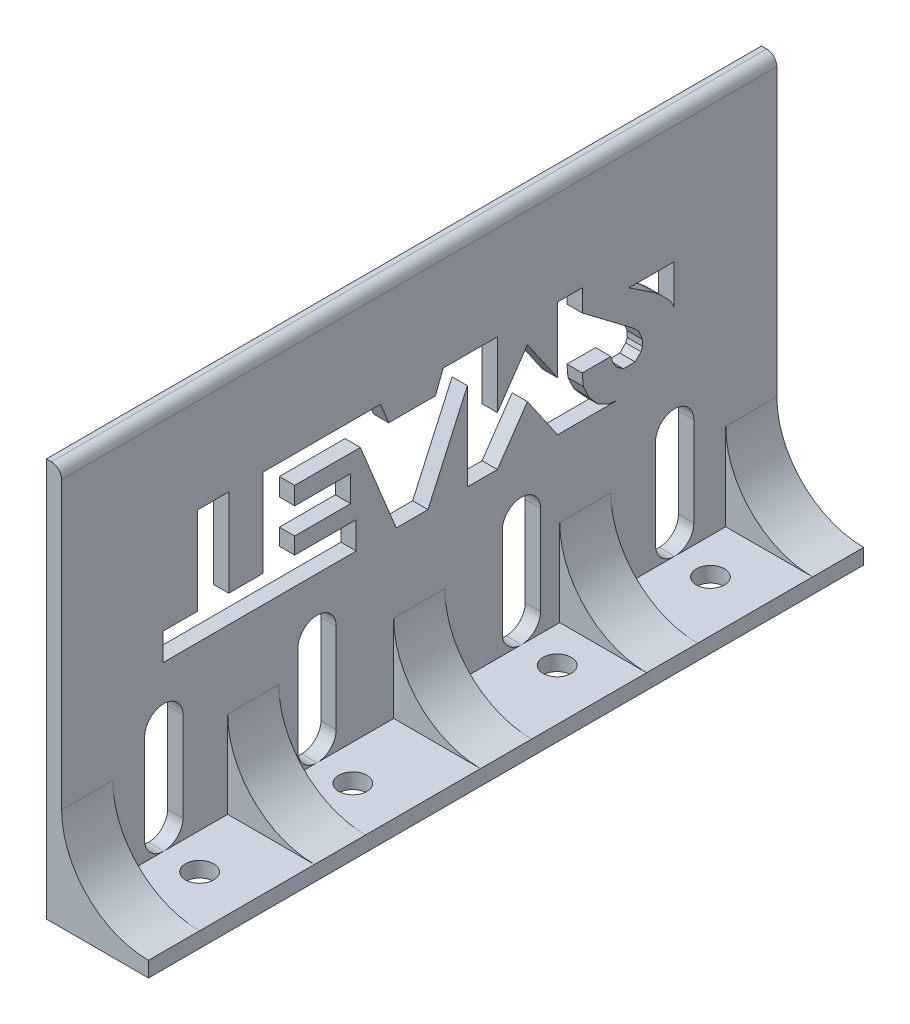
SolidWorks part; units mm, degrees
ref_plane "Front Plane" through (0, 0, 0) normal (0, 0, 1) x (1, 0, 0)
ref_plane "Top Plane" through (0, 0, 0) normal (0, 1, 0) x (1, 0, 0)
ref_plane "Right Plane" through (0, 0, 0) normal (1, 0, 0) x (0, 0, -1)
sketch "Sketch1" plane through (0, 0, 0) normal (0, 1, 0) x (1, 0, 0)
  line L1 (0, 140) -> (20, 140)
  line L2 (0, 140) -> (0, 0)
  line L3 (0, 0) -> (20, 0)
  line L4 (20, 140) -> (20, 0)
  dimension "D1" = 140
  dimension "D2" = 20
extrude "Boss-Extrude1" add sketch "Sketch1" along normal blind 3
sketch "Sketch2" plane through (0, 3, 0) normal (0, 1, 0) x (1, 0, 0)
  line L0 (0, 0) -> (20, 0) construction
  line L1 (0, 140) -> (3, 140)
  line L2 (0, 140) -> (0, 0)
  line L3 (0, 0) -> (3, 0)
  line L4 (3, 140) -> (3, 0)
  dimension "D1" = 3
extrude "Boss-Extrude2" add sketch "Sketch2" along normal blind 75
sketch "Sketch4" plane through (0, 0, 0) normal (0, -1, 0) x (1, 0, 0)
  line L0 (10, -120) -> (10, -20) construction
  line L1 (0, 0) -> (20, 0) construction
  line L2 (0, -140) -> (0, 0) construction
  circle A0 centre (10, -20) radius 2.75
  circle A2 centre (10, -50) radius 2.75
  circle A3 centre (10, -120) radius 2.75
  circle A4 centre (10, -90) radius 2.75
  point P6 (10, -70)
  point P11 (10, 0)
  point P12 (0, 0)
  point P15 (0, -70)
  dimension "D1" = 30
  dimension "D4" = 5.5
  dimension "D2" = 30
  dimension "D3" = 100
extrude "Cut-Extrude1" cut sketch "Sketch4" against normal blind 10
sketch "Sketch11" plane through (0, 0, 0) normal (-1, 0, 0) x (0, 0, 1)
  line L0 (-82.1667, -2) -> (-330.8333, -2) construction
  line L1 (-19.8745, 35.0495) -> (-57.6685, 35.0495)
  line L2 (-57.6685, 35.0495) -> (-57.6685, 40.3757)
  line L3 (-57.6685, 40.3757) -> (-45.6207, 40.3757)
  line L4 (-45.6207, 40.3757) -> (-45.6207, 43.6286)
  line L5 (-45.6207, 43.6286) -> (-56.568, 43.6286)
  line L6 (-56.568, 43.6286) -> (-56.568, 48.7277)
  line L7 (-56.568, 48.7277) -> (-45.6207, 48.7277)
  line L8 (-45.6207, 48.7277) -> (-45.6207, 52.2076)
  line L9 (-45.6207, 52.2076) -> (-58.4743, 52.2076)
  line L10 (-58.4743, 52.2076) -> (-65.496, 35.0495)
  line L11 (-65.496, 35.0495) -> (-71.704, 35.0495)
  line L12 (-71.704, 35.0495) -> (-79.4314, 52.2076)
  line L13 (-79.4314, 52.2076) -> (-79.4314, 35.0495)
  line L14 (-91.18, 43.6286) -> (-97.089, 35.0495)
  line L15 (-97.089, 35.0495) -> (-108.6328, 35.0495)
  line L18 (-112.0774, 45.5887) -> (-101.912, 53.28)
  line L19 (-101.912, 53.28) -> (-101.912, 57.5529)
  line L20 (-101.912, 57.5529) -> (-97.089, 57.5529)
  line L21 (-97.089, 57.5529) -> (-97.089, 44.7009)
  line L22 (-97.089, 44.7009) -> (-91.18, 53.28)
  line L23 (-91.18, 53.28) -> (-85.2893, 44.7009)
  line L24 (-85.2893, 44.7009) -> (-85.2893, 57.5529)
  line L25 (-62.4205, 57.5529) -> (-39.4375, 57.5529)
  line L26 (-39.4375, 57.5529) -> (-39.4375, 40.3757)
  line L27 (-39.4375, 40.3757) -> (-32.7115, 40.3757)
  line L28 (-32.7115, 40.3757) -> (-32.7115, 57.5529)
  line L29 (-32.7115, 57.5529) -> (-26.5718, 57.5529)
  line L30 (-26.5718, 57.5529) -> (-26.5718, 40.3757)
  line L31 (-26.5718, 40.3757) -> (-19.8745, 40.3757)
  line L32 (-19.8745, 40.3757) -> (-19.8745, 35.0495)
  line L33 (-119.871, 52.9786) -> (-111.0302, 52.9786)
  line L34 (-111.0302, 52.9786) -> (-115.1097, 50.2969)
  line L38 (-115.1097, 50.2969) -> (-115.8723, 49.7955)
  line L39 (-115.8723, 49.7955) -> (-117.2013, 48.7277)
  line L40 (-117.2013, 48.7277) -> (-119.0543, 46.8318)
  line L41 (-119.0543, 46.8318) -> (-119.5813, 46.0265)
  line L42 (-119.5813, 46.0265) -> (-119.871, 45.2733)
  line L44 (-119.871, 45.2733) -> (-119.871, 52.9786)
  line L45 (-85.2893, 57.5529) -> (-74.692, 57.5529)
  line L46 (-73.1717, 53.6017) -> (-74.692, 57.5529)
  line L47 (-64.0278, 53.6017) -> (-62.4205, 57.5529)
  line L48 (-64.0278, 53.6017) -> (-73.1717, 53.6017)
  line L52 (-91.18, 43.6286) -> (-85.2893, 35.0495)
  line L53 (-85.2893, 35.0495) -> (-79.4314, 35.0495)
  line L54 (-107.5115, 43.1186) -> (-101.912, 43.1186)
  line L55 (-101.912, 43.1186) -> (-102.1172, 40.7245)
  line L56 (-102.1172, 40.7245) -> (-103.2623, 38.2856)
  line L57 (-103.2623, 38.2856) -> (-104.8918, 36.4052)
  line L59 (-104.8918, 36.4052) -> (-106.9644, 35.3102)
  line L60 (-106.9644, 35.3102) -> (-108.6328, 35.0495)
  line L61 (-112.0774, 45.5887) -> (-112.9652, 44.7009)
  line L62 (-112.9652, 44.7009) -> (-113.708, 42.875)
  line L63 (-113.708, 42.875) -> (-113.708, 41.7402)
  line L64 (-113.708, 41.7402) -> (-113.4126, 40.9724)
  line L65 (-113.4126, 40.9724) -> (-112.2556, 39.8155)
  line L66 (-112.2556, 39.8155) -> (-109.9566, 39.8155)
  line L67 (-109.9566, 39.8155) -> (-108.6328, 40.7245)
  line L68 (-108.6328, 40.7245) -> (-108.0141, 41.6227)
  line L69 (-108.0141, 41.6227) -> (-107.5115, 43.1186)
extrude "Cut-Extrude5" cut sketch "Sketch11" against normal blind 10
sketch "Sketch13" plane through (3, 0, 0) normal (1, 0, 0) x (0, 0, -1)
  line L0 (0, 3) -> (140, 3) construction
  line L1 (22.75, 3) -> (17.25, 3) construction
  line L2 (122.75, 3) -> (117.25, 3) construction
  line L3 (92.75, 3) -> (87.25, 3) construction
  line L4 (52.75, 3) -> (47.25, 3) construction
  line L6 (16.25, 3) -> (23.75, 3)
  line L7 (16.25, 3) -> (16.25, 28)
  line L8 (16.25, 28) -> (23.75, 28)
  line L9 (23.75, 3) -> (23.75, 28)
  line L10 (46.25, 3) -> (53.75, 3)
  line L11 (46.25, 3) -> (46.25, 28)
  line L12 (46.25, 28) -> (53.75, 28)
  line L13 (53.75, 3) -> (53.75, 28)
  line L14 (86.25, 3) -> (93.75, 3)
  line L15 (86.25, 3) -> (86.25, 28)
  line L16 (86.25, 28) -> (93.75, 28)
  line L17 (93.75, 3) -> (93.75, 28)
  line L18 (116.25, 3) -> (123.75, 3)
  line L19 (116.25, 3) -> (116.25, 28)
  line L20 (116.25, 28) -> (123.75, 28)
  line L21 (123.75, 3) -> (123.75, 28)
  point P0 (20, 3)
  point P1 (90, 3)
  point P6 (50, 3)
  point P7 (120, 3)
  point P30 (0, 0)
  point P31 (0, 0)
  point P32 (0, 0)
  dimension "D1" = 25
  dimension "D2" = 7.5
extrude "Cut-Extrude6" cut sketch "Sketch13" against normal through all
sketch "Sketch14" plane through (0, 0, 0) normal (0, 0, 1) x (1, 0, 0)
  line L0 (3, 3) -> (3, 20)
  line L1 (3, 78) -> (3, 3) construction
  line L3 (20, 3) -> (3, 3)
  arc A0 (3, 20) -> (20, 3) centre (20, 20) ccw
  point P6 (3, 20)
  point P9 (0, 0)
extrude "Boss-Extrude3" add sketch "Sketch14" against normal blind 10
ref_plane "Plane1" through (0, 0, -70) normal (0, 0, 1) x (1, 0, 0)
mirror "Mirror1" about plane through (0, 0, -70) normal (0, 0, 1) of "Boss-Extrude3"
sketch "Sketch15" plane through (0, 0, -70) normal (0, 0, 1) x (1, 0, 0)
  line L2 (3, 20) -> (3, 3)
  line L3 (3, 3) -> (20, 3)
  line L4 (3, 20) -> (3, 3)
  line L5 (3, 3) -> (20, 3)
  arc A1 (3, 20) -> (20, 3) centre (20, 20) ccw
  arc A2 (3, 20) -> (20, 3) centre (20, 20) ccw
  dimension "D1" = 0
extrude "Boss-Extrude4" add sketch "Sketch15" along normal mid plane 10
fillet "Fillet1" radius 3.75 16 edges at (1.5, 3, -116.25) (1.5, 28, -116.25) (1.5, 28, -123.75) (1.5, 3, -123.75) (1.5, 3, -93.75) (1.5, 3, -86.25) (1.5, 28, -93.75) (1.5, 28, -86.25) (1.5, 3, -53.75) (1.5, 3, -46.25) (1.5, 28, -46.25) (1.5, 28, -53.75) (1.5, 3, -23.75) (1.5, 3, -16.25) (1.5, 28, -16.25) (1.5, 28, -23.75)
ref_plane "Plane2" through (0, 0, -37.5) normal (0, 0, -1) x (-1, 0, 0)
sketch "Sketch16" plane through (0, 0, -37.5) normal (0, 0, -1) x (-1, 0, 0)
  line L2 (-20, 3) -> (-3, 3)
  line L3 (-3, 3) -> (-3, 20)
  line L4 (-20, 3) -> (-3, 3)
  line L5 (-3, 3) -> (-3, 20)
  arc A1 (-20, 3) -> (-3, 20) centre (-20, 20) ccw
  arc A2 (-20, 3) -> (-3, 20) centre (-20, 20) ccw
  dimension "D1" = 0
extrude "Boss-Extrude5" add sketch "Sketch16" along normal mid plane 10
mirror "Mirror2" about plane through (0, 0, -70) normal (0, 0, 1) of "Boss-Extrude5"
fillet "Fillet2" radius 2 1 edges at (3, 78, -70)
